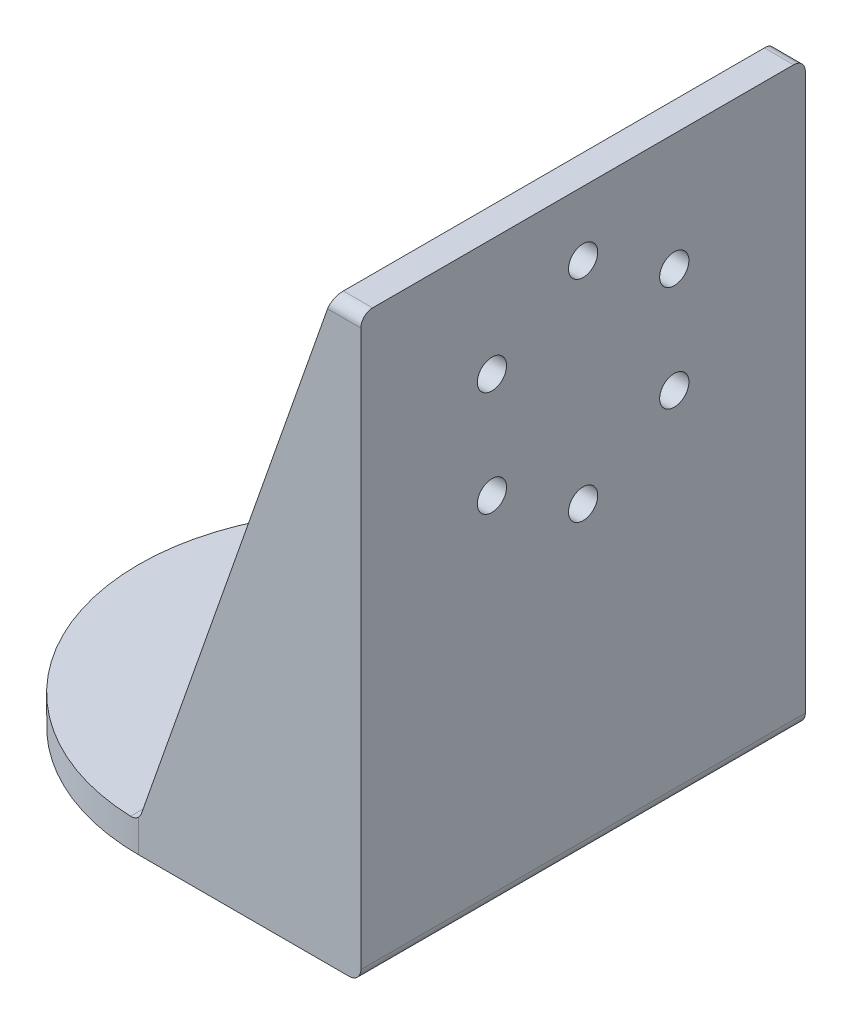
SolidWorks part; units mm, degrees
ref_plane "Спереди" through (0, 0, 0) normal (0, 0, 1) x (1, 0, 0)
ref_plane "Сверху" through (0, 0, 0) normal (0, 1, 0) x (1, 0, 0)
ref_plane "Справа" through (0, 0, 0) normal (1, 0, 0) x (0, 0, -1)
sketch "Эскиз3" plane through (0, 0, 0) normal (0, 0, 1) x (1, 0, 0)
  line L1 (76, 0) -> (0, 0)
  line L3 (71, 5) -> (0, 5)
  line L4 (0, 0) -> (0, 5)
  line L8 (76, 0) -> (76, 99)
  line L9 (76, 99) -> (71, 99)
  line L10 (71, 5) -> (71, 99)
  point P0 (0, 0)
  dimension "D1" = 5
  dimension "D2" = 76
  dimension "D3" = 5
  dimension "D4" = 99
extrude "Бобышка-Вытянуть1" add sketch "Эскиз3" along normal blind 76
fillet "Скругление1" radius 38 2 edges at (0, 2.5, 0) (0, 2.5, 76)
ref_plane "Плоскость7" through (0, 0, 0) normal (0, 0, -1) x (-1, 0, 0)
ref_plane "Плоскость8" through (0, 0, 76) normal (0, 0, 1) x (1, 0, 0)
sketch "Эскиз4" plane through (0, 0, 76) normal (0, 0, 1) x (1, 0, 0)
  line L0 (71, 99) -> (38, 5)
rib "Ребро1" sketch "Эскиз4" sketch "Эскиз4" thickness 5 extrusion direction parallel to sketch draft on no parameters "D1"=5
sketch "Эскиз5" plane through (0, 0, 0) normal (0, 0, -1) x (-1, 0, 0)
  line L0 (-71, 99) -> (-38, 5)
rib "Ребро2" sketch "Эскиз5" sketch "Эскиз5" thickness 5 extrusion direction parallel to sketch draft on no parameters "D1"=5
sketch "Эскиз7" plane through (0, 5, 0) normal (0, 1, 0) x (1, 0, 0)
  line L0 (38, -38) -> (20, -38) construction
  circle A0 centre (38, -38) radius 18 construction
  circle A1 centre (20, -38) radius 2.5
  circle A2 centre (38, -38) radius 18
  circle A3 centre (29, -22.4115) radius 2.5
  circle A4 centre (38, -38) radius 18
  circle A5 centre (47, -22.4115) radius 2.5
  circle A6 centre (38, -38) radius 18
  circle A7 centre (56, -38) radius 2.5
  circle A8 centre (38, -38) radius 18
  circle A9 centre (47, -53.5885) radius 2.5
  circle A10 centre (38, -38) radius 18
  circle A11 centre (29, -53.5885) radius 2.5
  dimension "D1" = 36
  dimension "D2" = 5
  dimension "D3" = 6
extrude "Вырез-Вытянуть1" cut sketch "Эскиз7" against normal blind 10 contours A1 | A3 | A5 | A7 | A9 | A11
sketch "Эскиз8" plane through (76, 0, 0) normal (1, 0, 0) x (0, 0, -1)
  line L0 (-76, 0) -> (0, 0) construction
  line L1 (0, 0) -> (0, 99) construction
  line L2 (-38, 70) -> (-38, 52) construction
  circle A0 centre (-38, 70) radius 18 construction
  circle A1 centre (-38, 52) radius 2.5
  circle A2 centre (-38, 70) radius 18
  circle A3 centre (-53.5885, 61) radius 2.5
  circle A4 centre (-38, 70) radius 18
  circle A5 centre (-53.5885, 79) radius 2.5
  circle A6 centre (-38, 70) radius 18
  circle A7 centre (-38, 88) radius 2.5
  circle A8 centre (-38, 70) radius 18
  circle A9 centre (-22.4115, 79) radius 2.5
  circle A10 centre (-38, 70) radius 18
  circle A11 centre (-22.4115, 61) radius 2.5
  dimension "D1" = 36
  dimension "D2" = 70
  dimension "D4" = 5
  dimension "D3" = 38
  dimension "D5" = 6
extrude "Вырез-Вытянуть2" cut sketch "Эскиз8" against normal blind 10 contours A5 | A7 | A9 | A11 | A1 | A3
fillet "Скругление2" radius 2 1 edges at (76, 0, 38)
chamfer "Фаска1" distance 10 distance2 5 1 edges at (71, 5, 38) first distance on face at (71, 61, 51.0885)
fillet "Скругление3" radius 2 2 edges at (38, 5, 73.5) (38, 5, 2.5)
fillet "Скругление4" radius 2 2 edges at (73.5, 99, 0) (73.5, 99, 76)
